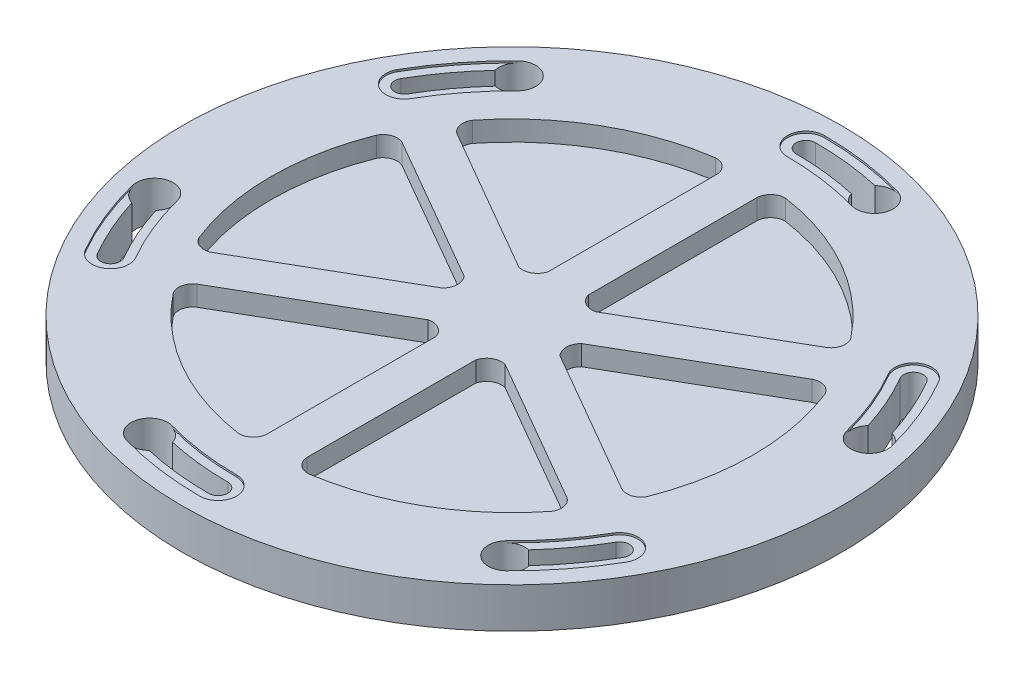
SolidWorks part; units mm, degrees
material "1060 Alloy"
ref_plane "Front Plane" through (0, 0, 0) normal (0, 0, 1) x (1, 0, 0)
ref_plane "Top Plane" through (0, 0, 0) normal (0, 1, 0) x (1, 0, 0)
ref_plane "Right Plane" through (0, 0, 0) normal (1, 0, 0) x (0, 0, -1)
sketch "Sketch1" plane through (0, 0, 0) normal (0, 1, 0) x (1, 0, 0)
  circle A0 centre (0, 0) radius 82
  arc A1 (0, 77.7102) -> (0, 68.5398) centre (0, 73.125) ccw
  arc A2 (0, 73.125) -> (19.8133, 70.3896) centre (0, 0) cw construction
  arc A3 (20.4672, 72.7124) -> (0, 75.5381) centre (0, 0) ccw construction
  arc A4 (19.1595, 68.0668) -> (0, 70.7119) centre (0, 0) ccw construction
  arc A5 (19.1595, 68.0668) -> (20.4672, 72.7124) centre (19.8133, 70.3896) ccw construction
  arc A6 (0, 75.5381) -> (0, 70.7119) centre (0, 73.125) ccw construction
  arc A7 (0, 73.125) -> (19.8133, 70.3896) centre (0, 0) cw construction
  arc A8 (21.0557, 74.8033) -> (0, 77.7102) centre (0, 0) ccw construction
  arc A9 (18.571, 65.9759) -> (0, 68.5398) centre (0, 0) ccw construction
  arc A10 (18.571, 65.9759) -> (21.0557, 74.8033) centre (19.8133, 70.3896) ccw construction
  arc A11 (0, 77.7102) -> (0, 68.5398) centre (0, 73.125) ccw construction
  arc A12 (15.4421, 69.0052) -> (16.6259, 73.6857) centre (19.8133, 70.3896) ccw
  arc A13 (0, 75.5381) -> (0, 70.7119) centre (0, 73.125) ccw
  arc A14 (0, 70.7119) -> (15.4421, 69.0052) centre (0, 0) cw
  arc A15 (0, 75.5381) -> (16.6259, 73.6857) centre (0, 0) cw
  arc A16 (0, 77.7102) -> (21.0557, 74.8033) centre (0, 0) cw
  arc A17 (0, 68.5398) -> (18.571, 65.9759) centre (0, 0) cw
  circle A18 centre (0, 0) radius 82
  arc A19 (67.299, 38.8551) -> (59.3572, 34.2699) centre (63.3281, 36.5625) ccw
  arc A20 (65.4179, 37.769) -> (61.2383, 35.356) centre (63.3281, 36.5625) ccw
  arc A21 (65.4179, 37.769) -> (72.1266, 22.4444) centre (0, 0) cw
  arc A22 (67.299, 38.8551) -> (75.3094, 19.1669) centre (0, 0) cw
  arc A23 (67.4813, 21.1293) -> (72.1266, 22.4444) centre (70.8659, 18.036) ccw
  arc A24 (61.2383, 35.356) -> (67.4813, 21.1293) centre (0, 0) cw
  arc A25 (59.3572, 34.2699) -> (66.4223, 16.905) centre (0, 0) cw
  circle A26 centre (0, 0) radius 82
  arc A27 (67.299, -38.8551) -> (59.3572, -34.2699) centre (63.3281, -36.5625) ccw
  arc A28 (65.4179, -37.769) -> (61.2383, -35.356) centre (63.3281, -36.5625) ccw
  arc A29 (65.4179, -37.769) -> (55.5007, -51.2413) centre (0, 0) cw
  arc A30 (67.299, -38.8551) -> (54.2537, -55.6364) centre (0, 0) cw
  arc A31 (52.0392, -47.8759) -> (55.5007, -51.2413) centre (51.0525, -52.3537) ccw
  arc A32 (61.2383, -35.356) -> (52.0392, -47.8759) centre (0, 0) cw
  arc A33 (59.3572, -34.2699) -> (47.8513, -49.0709) centre (0, 0) cw
  circle A34 centre (0, 0) radius 82
  arc A35 (0, -77.7102) -> (0, -68.5398) centre (0, -73.125) ccw
  arc A36 (0, -75.5381) -> (0, -70.7119) centre (0, -73.125) ccw
  arc A37 (0, -75.5381) -> (-16.6259, -73.6857) centre (0, 0) cw
  arc A38 (0, -77.7102) -> (-21.0557, -74.8033) centre (0, 0) cw
  arc A39 (-15.4421, -69.0052) -> (-16.6259, -73.6857) centre (-19.8133, -70.3896) ccw
  arc A40 (0, -70.7119) -> (-15.4421, -69.0052) centre (0, 0) cw
  arc A41 (0, -68.5398) -> (-18.571, -65.9759) centre (0, 0) cw
  circle A42 centre (0, 0) radius 82
  arc A43 (-67.299, -38.8551) -> (-59.3572, -34.2699) centre (-63.3281, -36.5625) ccw
  arc A44 (-65.4179, -37.769) -> (-61.2383, -35.356) centre (-63.3281, -36.5625) ccw
  arc A45 (-65.4179, -37.769) -> (-72.1266, -22.4444) centre (0, 0) cw
  arc A46 (-67.299, -38.8551) -> (-75.3094, -19.1669) centre (0, 0) cw
  arc A47 (-67.4813, -21.1293) -> (-72.1266, -22.4444) centre (-70.8659, -18.036) ccw
  arc A48 (-61.2383, -35.356) -> (-67.4813, -21.1293) centre (0, 0) cw
  arc A49 (-59.3572, -34.2699) -> (-66.4223, -16.905) centre (0, 0) cw
  circle A50 centre (0, 0) radius 82
  arc A51 (-67.299, 38.8551) -> (-59.3572, 34.2699) centre (-63.3281, 36.5625) ccw
  arc A52 (-65.4179, 37.769) -> (-61.2383, 35.356) centre (-63.3281, 36.5625) ccw
  arc A53 (-65.4179, 37.769) -> (-55.5007, 51.2413) centre (0, 0) cw
  arc A54 (-67.299, 38.8551) -> (-54.2537, 55.6364) centre (0, 0) cw
  arc A55 (-52.0392, 47.8759) -> (-55.5007, 51.2413) centre (-51.0525, 52.3537) ccw
  arc A56 (-61.2383, 35.356) -> (-52.0392, 47.8759) centre (0, 0) cw
  arc A57 (-59.3572, 34.2699) -> (-47.8513, 49.0709) centre (0, 0) cw
  point P7 (10.0006, 72.4379)
  point P15 (10.0006, 72.4379)
  point P33 (-38.6857, 81.8884)
  point P111 (0, 0)
  dimension "D1" = 6
extrude "Boss-Extrude1" add sketch "Sketch1" along normal blind 10 contours A0 A57 A51 A54 A55 A49 A43 A46 A47 A41 A35 A38 A39 A33 A27 A30 A31 A25 A19 A22 A23 A17 A1 A16 A12 region at (0, 0, 0)
extrude "Boss-Extrude3" add sketch "Sketch1<4>" along normal blind 9.525 contours A43 A49 A47 A48 A44 A45 A46 region at (-71.7086, 0, 29.1755)
sketch "Sketch1<4>" plane through (0, 0, 0) normal (0, 1, 0) x (1, 0, 0) same geometry as "Sketch1"
pattern_circular "CirPattern1" count 6 over 360 about axis through (0, 10, 0) along (0, 1, 0) of "Boss-Extrude3"
sketch "Sketch2" plane through (0, 10, 0) normal (0, 1, 0) x (1, 0, 0)
  line L0 (-28.4808, 10.6699) -> (-51.0159, 23.6805)
  line L1 (-28.4808, 10.6699) -> (-14.6202, 2.6675)
  line L2 (-14.6202, -2.6675) -> (-28.4808, -10.6699)
  line L3 (-28.4808, -10.6699) -> (-51.0159, -23.6805)
  line L4 (-5, 30) -> (-5, 56.0213)
  line L5 (-5, 30) -> (-5, 13.9952)
  line L6 (-9.6202, 11.3277) -> (-23.4808, 19.3301)
  line L7 (-23.4808, 19.3301) -> (-46.0159, 32.3408)
  line L8 (-23.4808, -19.3301) -> (-9.6202, -11.3277)
  line L9 (-5, -13.9952) -> (-5, -30)
  line L10 (-23.4808, -19.3301) -> (-46.0159, -32.3408)
  line L11 (-5, -30) -> (-5, -56.0213)
  line L12 (23.4808, 19.3301) -> (46.0159, 32.3408)
  line L13 (23.4808, 19.3301) -> (9.6202, 11.3277)
  line L14 (5, 13.9952) -> (5, 30)
  line L15 (5, 30) -> (5, 56.0213)
  line L16 (28.4808, -10.6699) -> (51.0159, -23.6805)
  line L17 (28.4808, -10.6699) -> (14.6202, -2.6675)
  line L18 (14.6202, 2.6675) -> (28.4808, 10.6699)
  line L19 (28.4808, 10.6699) -> (51.0159, 23.6805)
  line L20 (5, -30) -> (5, -56.0213)
  line L21 (5, -30) -> (5, -13.9952)
  line L22 (9.6202, -11.3277) -> (23.4808, -19.3301)
  line L23 (23.4808, -19.3301) -> (46.0159, -32.3408)
  arc A0 (-47.034, -37.2532) -> (-8.7452, -59.3593) centre (0, 0) ccw
  arc A1 (-9.6202, -11.3277) -> (-5, -13.9952) centre (-8.6438, -14.9716) cw
  arc A2 (-47.034, -37.2532) -> (-8.7452, -59.3593) centre (0, 0) ccw
  arc A3 (-47.034, -37.2532) -> (-46.0159, -32.3408) centre (-44.0688, -35.3061) cw
  arc A4 (-5, -56.0213) -> (-8.7452, -59.3593) centre (-8.5416, -55.8177) cw
  arc A5 (-55.7792, 22.1061) -> (-51.0159, 23.6805) centre (-52.6103, 20.5116) cw
  arc A6 (-14.6202, 2.6675) -> (-14.6202, -2.6675) centre (-17.2877, 0) cw
  arc A7 (-51.0159, -23.6805) -> (-55.7792, -22.1061) centre (-52.6103, -20.5116) cw
  arc A8 (-47.034, -37.2532) -> (-8.7452, -59.3593) centre (0, 0) ccw
  arc A9 (-8.7452, 59.3593) -> (-5, 56.0213) centre (-8.5416, 55.8177) cw
  arc A10 (-5, 13.9952) -> (-9.6202, 11.3277) centre (-8.6438, 14.9716) cw
  arc A11 (-46.0159, 32.3408) -> (-47.034, 37.2532) centre (-44.0688, 35.3061) cw
  arc A12 (-47.034, -37.2532) -> (-8.7452, -59.3593) centre (0, 0) ccw
  arc A13 (47.034, 37.2532) -> (46.0159, 32.3408) centre (44.0688, 35.3061) cw
  arc A14 (9.6202, 11.3277) -> (5, 13.9952) centre (8.6438, 14.9716) cw
  arc A15 (5, 56.0213) -> (8.7452, 59.3593) centre (8.5416, 55.8177) cw
  arc A16 (-47.034, -37.2532) -> (-8.7452, -59.3593) centre (0, 0) ccw
  arc A17 (55.7792, -22.1061) -> (51.0159, -23.6805) centre (52.6103, -20.5116) cw
  arc A18 (14.6202, -2.6675) -> (14.6202, 2.6675) centre (17.2877, 0) cw
  arc A19 (51.0159, 23.6805) -> (55.7792, 22.1061) centre (52.6103, 20.5116) cw
  arc A20 (-47.034, -37.2532) -> (-8.7452, -59.3593) centre (0, 0) ccw
  arc A21 (8.7452, -59.3593) -> (5, -56.0213) centre (8.5416, -55.8177) cw
  arc A22 (5, -13.9952) -> (9.6202, -11.3277) centre (8.6438, -14.9716) cw
  arc A23 (46.0159, -32.3408) -> (47.034, -37.2532) centre (44.0688, -35.3061) cw
  arc A24 (8.7452, -59.3593) -> (47.034, -37.2532) centre (0, 0) ccw
  arc A25 (8.7452, -59.3593) -> (47.034, -37.2532) centre (0, 0) ccw
  arc A26 (8.7452, -59.3593) -> (47.034, -37.2532) centre (0, 0) ccw
  arc A27 (8.7452, -59.3593) -> (47.034, -37.2532) centre (0, 0) ccw
  arc A28 (8.7452, -59.3593) -> (47.034, -37.2532) centre (0, 0) ccw
  arc A29 (8.7452, -59.3593) -> (47.034, -37.2532) centre (0, 0) ccw
  arc A30 (-55.7792, 22.1061) -> (-55.7792, -22.1061) centre (0, 0) ccw
  arc A31 (-55.7792, 22.1061) -> (-55.7792, -22.1061) centre (0, 0) ccw
  arc A32 (-55.7792, 22.1061) -> (-55.7792, -22.1061) centre (0, 0) ccw
  arc A33 (-55.7792, 22.1061) -> (-55.7792, -22.1061) centre (0, 0) ccw
  arc A34 (-55.7792, 22.1061) -> (-55.7792, -22.1061) centre (0, 0) ccw
  arc A35 (-55.7792, 22.1061) -> (-55.7792, -22.1061) centre (0, 0) ccw
  arc A36 (-8.7452, 59.3593) -> (-47.034, 37.2532) centre (0, 0) ccw
  arc A37 (-8.7452, 59.3593) -> (-47.034, 37.2532) centre (0, 0) ccw
  arc A38 (-8.7452, 59.3593) -> (-47.034, 37.2532) centre (0, 0) ccw
  arc A39 (-8.7452, 59.3593) -> (-47.034, 37.2532) centre (0, 0) ccw
  arc A40 (-8.7452, 59.3593) -> (-47.034, 37.2532) centre (0, 0) ccw
  arc A41 (-8.7452, 59.3593) -> (-47.034, 37.2532) centre (0, 0) ccw
  arc A42 (47.034, 37.2532) -> (8.7452, 59.3593) centre (0, 0) ccw
  arc A43 (47.034, 37.2532) -> (8.7452, 59.3593) centre (0, 0) ccw
  arc A44 (47.034, 37.2532) -> (8.7452, 59.3593) centre (0, 0) ccw
  arc A45 (47.034, 37.2532) -> (8.7452, 59.3593) centre (0, 0) ccw
  arc A46 (47.034, 37.2532) -> (8.7452, 59.3593) centre (0, 0) ccw
  arc A47 (47.034, 37.2532) -> (8.7452, 59.3593) centre (0, 0) ccw
  arc A48 (55.7792, -22.1061) -> (55.7792, 22.1061) centre (0, 0) ccw
  arc A49 (55.7792, -22.1061) -> (55.7792, 22.1061) centre (0, 0) ccw
  arc A50 (55.7792, -22.1061) -> (55.7792, 22.1061) centre (0, 0) ccw
  arc A51 (55.7792, -22.1061) -> (55.7792, 22.1061) centre (0, 0) ccw
  arc A52 (55.7792, -22.1061) -> (55.7792, 22.1061) centre (0, 0) ccw
  arc A53 (55.7792, -22.1061) -> (55.7792, 22.1061) centre (0, 0) ccw
  point P83 (0, 0)
  dimension "D1" = 6
extrude "Cut-Extrude1" cut sketch "Sketch2" against normal blind 5 contours A5 A30 A7 L3 L2 A6 L1 L0 | A9 A36 A11 L7 L6 A10 L5 L4 | A13 A42 A15 L15 L14 A14 L13 L12 | A17 A48 A19 L19 L18 A18 L17 L16 | A21 A24 A23 L23 L22 A22 L21 L20 | A4 L11 L9 A1 L8 L10 A3 A0 region at (-42.1694, 10, 0) region at (-21.0847, 10, -36.5198) region at (-21.0847, 10, 36.5198) region at (21.0847, 10, -36.5198) region at (42.1694, 10, 0) region at (21.0847, 10, 36.5198)
